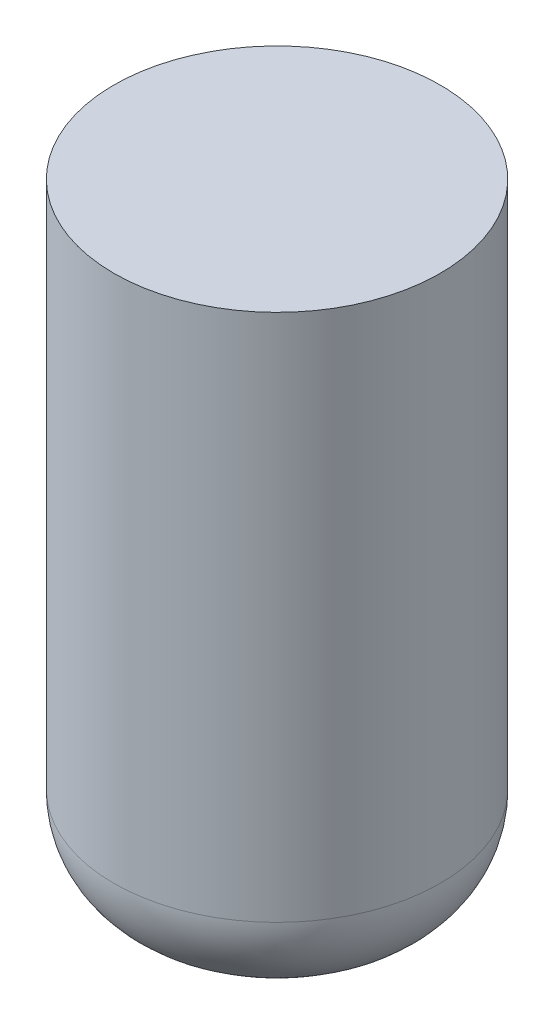
SolidWorks part; units mm, degrees
ref_plane "Front Plane" through (0, 0, 0) normal (0, 0, 1) x (1, 0, 0)
ref_plane "Top Plane" through (0, 0, 0) normal (0, 1, 0) x (1, 0, 0)
ref_plane "Right Plane" through (0, 0, 0) normal (1, 0, 0) x (0, 0, -1)
sketch "Sketch1" plane through (0, 0, 0) normal (0, 1, 0) x (1, 0, 0)
  circle A0 centre (0, 0) radius 2.1
  dimension "D1" = 4.2
extrude "Boss-Extrude1" add sketch "Sketch1" along normal blind 8
fillet "Fillet2" radius 1.2 1 edges at (0, 0, 2.1)
